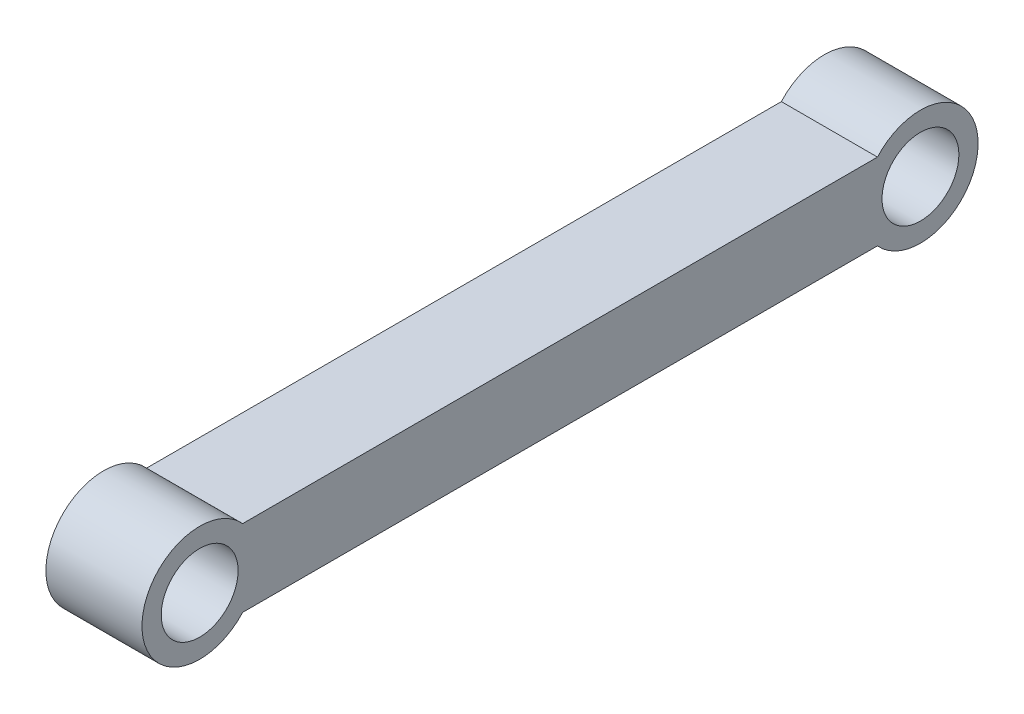
SolidWorks part; units mm, degrees
material "Thornel Mat VMA"
ref_plane "Front Plane" through (0, 0, 0) normal (0, 0, 1) x (1, 0, 0)
ref_plane "Top Plane" through (0, 0, 0) normal (0, 1, 0) x (1, 0, 0)
ref_plane "Right Plane" through (0, 0, 0) normal (1, 0, 0) x (0, 0, -1)
sketch "LinkFrame" plane through (0, 0, 0) normal (1, 0, 0) x (0, 0, -1)
  line L0 (-490.3455, -226.2633) -> (259.6545, -226.2633) construction
  line L1 (-445.6242, -186.2633) -> (214.9331, -186.2633)
  line L2 (-445.6242, -266.2633) -> (214.9331, -266.2633)
  arc A1 (214.9331, -266.2633) -> (214.9331, -186.2633) centre (259.6545, -226.2633) ccw
  arc A2 (-445.6242, -186.2633) -> (-445.6242, -266.2633) centre (-490.3455, -226.2633) ccw
  circle A5 centre (-490.3455, -226.2633) radius 40
  circle A6 centre (259.6545, -226.2633) radius 40
  dimension "D1" = 120
  dimension "D2" = 120
  dimension "D5" = 80
  dimension "D6" = 80
  dimension "D3" = 750
  dimension "D4" = 80
  dimension "D7" = 44.7214
  dimension "D8" = 44.7214
extrude "Boss-Extrude1" add sketch "LinkFrame" along normal blind 100
equation "\"D1@LinkFrame\" = 1.5 * \"HoleMountDiameter@PrintingPress.Assembly\""
equation "\"D2@LinkFrame\" = 1.5 * \"HoleMountDiameter@PrintingPress.Assembly\""
equation "\"LinkLength\" = 75cm"
equation "\"D3@LinkFrame\" = \"LinkLength\""
equation "\"D4@LinkFrame\" = \"HoleMountDiameter@PrintingPress.Assembly\""
equation "\"D5@LinkFrame\"=\"HoleMountDiameter@PrintingPress.Assembly\""
equation "\"D6@LinkFrame\"=\"HoleMountDiameter@PrintingPress.Assembly\""
equation "\"D1@Boss-Extrude1\"=\"RivetLength@PrintingPress.Assembly\""
